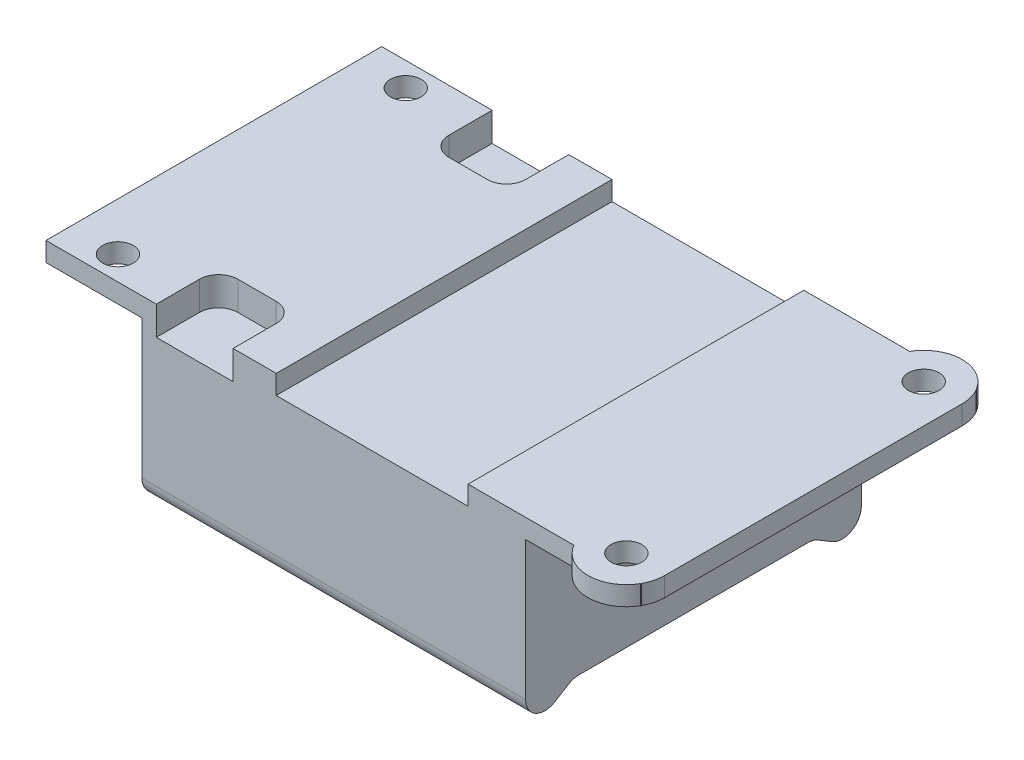
SolidWorks part; units mm, degrees
material "PEI"
ref_plane "Front Plane" through (0, 0, 0) normal (0, 0, 1) x (1, 0, 0)
ref_plane "Top Plane" through (0, 0, 0) normal (0, 1, 0) x (1, 0, 0)
ref_plane "Right Plane" through (0, 0, 0) normal (1, 0, 0) x (0, 0, -1)
sketch "Sketch1" plane through (0, 0, 0) normal (0, 1, 0) x (1, 0, 0)
  line L1 (20, -17.5) -> (-20, -17.5)
  line L2 (20, -17.5) -> (20, 17.5)
  line L3 (20, 17.5) -> (-20, 17.5)
  line L4 (-20, -17.5) -> (-20, 17.5)
  line L5 (20, -17.5) -> (-20, 17.5) construction
  line L6 (20, 17.5) -> (-20, -17.5) construction
  point P0 (0, 0)
  dimension "D1" = 35
  dimension "D2" = 40
extrude "Boss-Extrude1" add sketch "Sketch1" against normal blind 20
sketch "Sketch2" plane through (20, 0, 0) normal (1, 0, 0) x (0, 0, -1)
  line L0 (-17.5, -20) -> (-12.5, -17)
  line L1 (-12.5, -17) -> (12.5, -17)
  line L2 (0, -17) -> (0, -20)
  line L3 (17.5, -20) -> (12.5, -17)
  line L4 (17.5, 0) -> (-17.5, 0)
  line L5 (-17.5, 0) -> (-17.5, -20)
  line L6 (-17.5, -20) -> (17.5, -20)
  line L7 (17.5, -20) -> (17.5, 0)
  line L8 (17.5, 0) -> (-17.5, 0)
  line L9 (-17.5, 0) -> (-17.5, -20)
  line L10 (-17.5, -20) -> (17.5, -20)
  line L11 (17.5, -20) -> (17.5, 0)
  line M7 (-17.5, -20) -> (17.5, -20)
  dimension "D2" = 5
  dimension "D3" = 3
  dimension "D1" = 0
extrude "Cut-Extrude1" cut sketch "Sketch2" against normal through all and the other way through all contours L2 L1 L0 M7 | L3 L1 L2 M7 region at (20, -18.5833, 7.5694) region at (20, -18.5833, -7.5694)
fillet "Fillet1" radius 2 4 edges at (0, -17, 12.5) (0, -17, -12.5) (0, -20, -17.5) (0, -20, 17.5)
sketch "Sketch4" plane through (-20, 0, 0) normal (-1, 0, 0) x (0, 0, 1)
  line L1 (-17.5, 0) -> (17.5, 0)
  line L2 (-17.5, 0) -> (-17.5, -2)
  line L3 (-17.5, -2) -> (17.5, -2)
  line L4 (17.5, 0) -> (17.5, -2)
  line L6 (-17.5, 0) -> (-17.5, -16.4676)
  line L7 (-14.471, -18.1826) -> (-12.975, -17.285)
  line L8 (-11.946, -17) -> (11.946, -17)
  line L9 (12.975, -17.285) -> (14.471, -18.1826)
  line L10 (17.5, -16.4676) -> (17.5, 0)
  line L11 (17.5, 0) -> (-17.5, 0)
  line L12 (-17.5, 0) -> (-17.5, -16.4676)
  line L13 (-14.471, -18.1826) -> (-12.975, -17.285)
  line L14 (-11.946, -17) -> (11.946, -17)
  line L15 (12.975, -17.285) -> (14.471, -18.1826)
  line L16 (17.5, -16.4676) -> (17.5, 0)
  line L17 (17.5, 0) -> (-17.5, 0)
  arc A4 (-17.5, -16.4676) -> (-14.471, -18.1826) centre (-15.5, -16.4676) ccw
  arc A5 (-11.946, -17) -> (-12.975, -17.285) centre (-11.946, -19) ccw
  arc A6 (12.975, -17.285) -> (11.946, -17) centre (11.946, -19) ccw
  arc A7 (14.471, -18.1826) -> (17.5, -16.4676) centre (15.5, -16.4676) ccw
  arc A8 (-17.5, -16.4676) -> (-14.471, -18.1826) centre (-15.5, -16.4676) ccw
  arc A9 (-11.946, -17) -> (-12.975, -17.285) centre (-11.946, -19) ccw
  arc A10 (12.975, -17.285) -> (11.946, -17) centre (11.946, -19) ccw
  arc A11 (14.471, -18.1826) -> (17.5, -16.4676) centre (15.5, -16.4676) ccw
  line M12 (-17.5, 0) -> (-17.5, -16.4676)
  line M20 (17.5, -16.4676) -> (17.5, 0)
  line M21 (17.5, 0) -> (-17.5, 0)
  dimension "D2" = 2
  dimension "D1" = 0
extrude "Boss-Extrude2" add sketch "Sketch4" along normal blind 10 contours L3 M12 M20 M21 region at (-20, -1, 0)
sketch "Sketch5" plane through (20, 0, 0) normal (1, 0, 0) x (0, 0, -1)
  line L1 (-17.5, 0) -> (17.5, 0)
  line L2 (-17.5, 0) -> (-17.5, -2)
  line L3 (-17.5, -2) -> (17.5, -2)
  line L4 (17.5, 0) -> (17.5, -2)
  line L6 (12.975, -17.285) -> (14.471, -18.1826)
  line L7 (17.5, -16.4676) -> (17.5, 0)
  line L8 (17.5, 0) -> (-17.5, 0)
  line L9 (-17.5, 0) -> (-17.5, -16.4676)
  line L10 (-14.471, -18.1826) -> (-12.975, -17.285)
  line L11 (-11.946, -17) -> (11.946, -17)
  line L12 (12.975, -17.285) -> (14.471, -18.1826)
  line L13 (17.5, -16.4676) -> (17.5, 0)
  line L14 (17.5, 0) -> (-17.5, 0)
  line L15 (-17.5, 0) -> (-17.5, -16.4676)
  line L16 (-14.471, -18.1826) -> (-12.975, -17.285)
  line L17 (-11.946, -17) -> (11.946, -17)
  arc A4 (14.471, -18.1826) -> (17.5, -16.4676) centre (15.5, -16.4676) ccw
  arc A5 (-17.5, -16.4676) -> (-14.471, -18.1826) centre (-15.5, -16.4676) ccw
  arc A6 (-11.946, -17) -> (-12.975, -17.285) centre (-11.946, -19) ccw
  arc A7 (12.975, -17.285) -> (11.946, -17) centre (11.946, -19) ccw
  arc A8 (14.471, -18.1826) -> (17.5, -16.4676) centre (15.5, -16.4676) ccw
  arc A9 (-17.5, -16.4676) -> (-14.471, -18.1826) centre (-15.5, -16.4676) ccw
  arc A10 (-11.946, -17) -> (-12.975, -17.285) centre (-11.946, -19) ccw
  arc A11 (12.975, -17.285) -> (11.946, -17) centre (11.946, -19) ccw
  line M14 (17.5, -16.4676) -> (17.5, 0)
  line M15 (17.5, 0) -> (-17.5, 0)
  line M16 (-17.5, 0) -> (-17.5, -16.4676)
  dimension "D2" = 2
  dimension "D1" = 0
extrude "Boss-Extrude3" add sketch "Sketch5" along normal blind 12 contours L3 M16 M14 M15 region at (20, -1, 0)
sketch "Sketch6" plane through (0, -2, 0) normal (0, -1, 0) x (1, 0, 0)
  line L0 (0, 0) -> (-25, 0)
  line L1 (-25, 0) -> (-25, 15)
  line L4 (-20, -17.5) -> (-20, 17.5)
  line L5 (-20, 17.5) -> (-30, 17.5)
  line L6 (-30, 17.5) -> (-30, -17.5)
  line L7 (-30, -17.5) -> (-20, -17.5)
  line L8 (-20, -17.5) -> (-20, 17.5)
  line L9 (-20, 17.5) -> (-30, 17.5)
  line L10 (-30, 17.5) -> (-30, -17.5)
  line L11 (-30, -17.5) -> (-20, -17.5)
  line L12 (20, -11.946) -> (20, 11.946)
  line L13 (20, 11.946) -> (-20, 11.946)
  line L14 (-20, 11.946) -> (-20, -11.946)
  line L15 (-20, -11.946) -> (20, -11.946)
  line L16 (20, -11.946) -> (20, 11.946)
  line L17 (20, 11.946) -> (-20, 11.946)
  line L18 (-20, 11.946) -> (-20, -11.946)
  line L19 (-20, -11.946) -> (20, -11.946)
  circle A0 centre (-25, 15) radius 1.6
  circle A1 centre (-25, -15) radius 1.6
  dimension "D5" = 3.2
  dimension "D3" = 15
  dimension "D4" = 25
  dimension "D1" = 0
  dimension "D2" = 0
extrude "Cut-Extrude2" cut sketch "Sketch6" against normal blind 10 contours A1 | A0 region at (-26.0994, -2, 16.0994) region at (-25, -2, -15)
sketch "Sketch7" plane through (0, 0, 0) normal (0, 1, 0) x (1, 0, 0)
  line L0 (-25, -15) -> (-14.5, -15)
  line L1 (-14.5, -15) -> (-14.5, -14.5)
  line L2 (0, 0) -> (-16.7205, 0)
  line L3 (-10.5, -19) -> (-18.5, -19)
  line L4 (32, 17.5) -> (-30, 17.5)
  line L5 (-30, 17.5) -> (-30, -17.5)
  line L6 (-30, -17.5) -> (32, -17.5)
  line L7 (32, -17.5) -> (32, 17.5)
  line L8 (32, 17.5) -> (-30, 17.5)
  line L9 (-30, 17.5) -> (-30, -17.5)
  line L10 (-30, -17.5) -> (32, -17.5)
  line L11 (32, -17.5) -> (32, 17.5)
  line L12 (-10.5, -19) -> (-10.5, -11)
  line L13 (-10.5, -11) -> (-18.5, -11)
  line L14 (-18.5, -19) -> (-18.5, -11)
  line L15 (-10.5, -19) -> (-18.5, -11) construction
  line L16 (-10.5, -11) -> (-18.5, -19) construction
  line L17 (-10.5, 19) -> (-18.5, 19)
  line L18 (-18.5, 19) -> (-18.5, 11)
  line L19 (-10.5, 19) -> (-10.5, 11)
  line L20 (-10.5, 11) -> (-18.5, 11)
  dimension "D4" = 8
  dimension "D2" = 0.5
  dimension "D3" = 10.5
  dimension "D5" = 8
  dimension "D1" = 0
extrude "Cut-Extrude3" cut sketch "Sketch7" against normal blind 3 contours L20 L19 L8 L18 | L12 L13 L14 L3 region at (-14.5, 0, -14.25)
sketch "Sketch8" plane through (0, 0, 17.5) normal (0, 0, 1) x (1, 0, 0)
  line L0 (-10.5, 0) -> (32, 0) construction
  line L1 (14, 2) -> (-6, 2)
  line L2 (14, 2) -> (14, -2)
  line L3 (14, -2) -> (-6, -2)
  line L4 (-6, 2) -> (-6, -2)
  line L5 (14, 2) -> (-6, -2) construction
  line L6 (14, -2) -> (-6, 2) construction
  line L12 (-10.5, -3) -> (-18.5, -3)
  line L13 (-18.5, -3) -> (-18.5, 0)
  line L14 (-18.5, 0) -> (-30, 0)
  line L15 (-30, 0) -> (-30, -2)
  line L16 (-30, -2) -> (-20, -2)
  line L17 (-20, -2) -> (-20, -16.4676)
  line L18 (-20, -16.4676) -> (20, -16.4676)
  line L19 (20, -16.4676) -> (20, -2)
  line L20 (20, -2) -> (32, -2)
  line L21 (32, -2) -> (32, 0)
  line L22 (32, 0) -> (-10.5, 0)
  line L23 (-10.5, 0) -> (-10.5, -3)
  line L24 (-10.5, -3) -> (-18.5, -3)
  line L25 (-18.5, -3) -> (-18.5, 0)
  line L26 (-18.5, 0) -> (-30, 0)
  line L27 (-30, 0) -> (-30, -2)
  line L28 (-30, -2) -> (-20, -2)
  line L29 (-20, -2) -> (-20, -16.4676)
  line L30 (-20, -16.4676) -> (20, -16.4676)
  line L31 (20, -16.4676) -> (20, -2)
  line L32 (20, -2) -> (32, -2)
  line L33 (32, -2) -> (32, 0)
  line L34 (32, 0) -> (-10.5, 0)
  line L35 (-10.5, 0) -> (-10.5, -3)
  point P2 (4, 0)
  point P23 (-20, -9.2338)
  line M25 (32, 0) -> (-10.5, 0)
  dimension "D2" = 2
  dimension "D3" = 20
  dimension "D4" = 24
  dimension "D1" = 0
extrude "Cut-Extrude5" cut sketch "Sketch8" against normal through all contours L4 L3 L2 M25 region at (4, -1, 17.5)
fillet "Fillet2" radius 2 4 edges at (-18.5, -1.5, 11) (-10.5, -1.5, 11) (-18.5, -1.5, -11) (-10.5, -1.5, -11)
sketch "Sketch10" plane through (0, -2, 0) normal (0, -1, 0) x (1, 0, 0)
  line L0 (-25, 15) -> (28.5, 15)
  line L1 (0, 0) -> (0, 15.5)
  line L2 (0, 15.5) -> (28.5, 15.5)
  line L3 (28.5, 15.5) -> (28.5, 15)
  line L4 (20, 17.5) -> (20, -17.5)
  line L5 (20, -17.5) -> (32, -17.5)
  line L6 (32, -17.5) -> (32, 17.5)
  line L7 (32, 17.5) -> (20, 17.5)
  line L8 (20, 17.5) -> (20, -17.5)
  line L9 (20, -17.5) -> (32, -17.5)
  line L10 (32, -17.5) -> (32, 17.5)
  line L11 (32, 17.5) -> (20, 17.5)
  line L12 (-20, -17.5) -> (-20, 17.5)
  line L13 (-20, 17.5) -> (-30, 17.5)
  line L14 (-30, 17.5) -> (-30, -17.5)
  line L15 (-30, -17.5) -> (-20, -17.5)
  line L16 (-20, -17.5) -> (-20, 17.5)
  line L17 (-20, 17.5) -> (-30, 17.5)
  line L18 (-30, 17.5) -> (-30, -17.5)
  line L19 (-30, -17.5) -> (-20, -17.5)
  line L20 (0, 0) -> (12.4483, 0)
  line L21 (32.5, 15.5) -> (32.5, -15.5)
  circle A2 centre (28.5, 15.5) radius 1.6
  circle A3 centre (28.5, 15.5) radius 4
  circle A4 centre (28.5, -15.5) radius 1.6
  circle A5 centre (28.5, -15.5) radius 4
  line M13 (32, -17.5) -> (32, 17.5)
  dimension "D4" = 3.2
  dimension "D6" = 8
  dimension "D3" = 53.5
  dimension "D5" = 15.5
  dimension "D1" = 0
  dimension "D2" = 0
extrude "Cut-Extrude6" cut sketch "Sketch10" against normal through all contours A4 | A2 region at (28.5, -2, -15.5)
extrude "Boss-Extrude4" add sketch "Sketch10<4>" against normal blind 2 contours L11 A3 | L10 A3 | A5 L9 | A5 L10 | A5 L21 A3 M13 region at (32.2545, -2, 0) region at (32.2011, -2, 15.5) region at (28.5, -2, -18.3201) region at (28.5, -2, 18.3201) region at (32.2011, -2, -15.5)
sketch "Sketch10<4>" plane through (0, -2, 0) normal (0, -1, 0) x (1, 0, 0) same geometry as "Sketch10"
